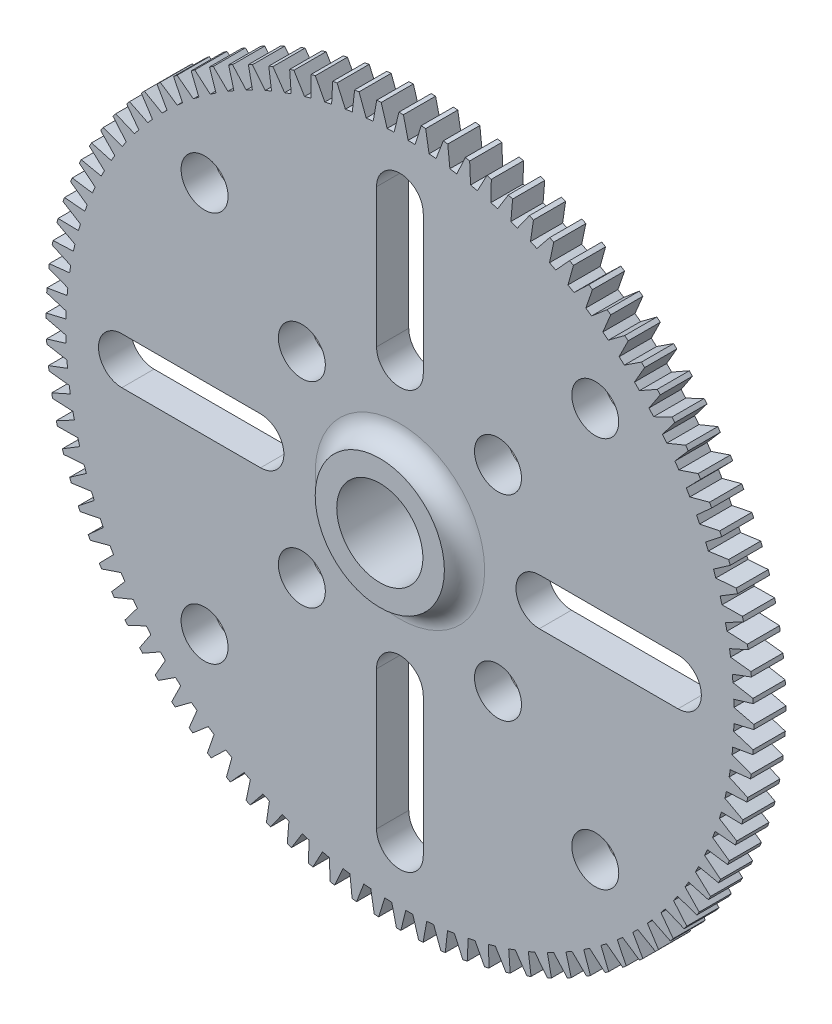
SolidWorks part; units mm, degrees
note: '?' marks a value the reader was unsure of.
ref_plane "Front Plane" through (0, 0, 0) normal (0, 0, 1) x (1, 0, 0)
ref_plane "Top Plane" through (0, 0, 0) normal (0, 1, 0) x (1, 0, 0)
ref_plane "Right Plane" through (0, 0, 0) normal (1, 0, 0) x (0, 0, -1)
sketch "Sketch1" plane through (0, 0, 0) normal (0, 0, 1) x (1, 0, 0)
  circle A0 centre (0, 0) radius 32.1437
  dimension "D1" = 64.2874
extrude "Extrude1" add sketch "Sketch1" along normal blind 2.921
sketch "Sketch3" plane through (0, 0, 0) normal (0, 0, -1) x (-1, 0, 0)
  line L0 (0, 0) -> (0, -32.1437) construction
  line L1 (0, 0) -> (2.2466, -32.0651) construction
  line L2 (0.7438, -30.3376) -> (0.3175, -32.1421)
  line L3 (1.3784, -30.3154) -> (1.9297, -32.0857)
  line L4 (0, 0) -> (1.124, -32.124) construction
  line L5 (0, -32.1437) -> (0.3175, -32.1421) construction
  line L6 (1.9297, -32.0857) -> (2.2466, -32.0651) construction
  circle A0 centre (0, 0) radius 32.1437 construction
  arc A1 (0.3175, -32.1421) -> (1.9297, -32.0857) centre (0, 0) ccw
  arc A2 (0.7438, -30.3376) -> (1.3784, -30.3154) centre (0, 0) ccw
  dimension "D1" = 0.3175
  dimension "D3" = 1.6132
  dimension "D4" = 1.8542
  dimension "D5" = 0.635
extrude "Cut-Extrude1" cut sketch "Sketch3" against normal through all
ref_axis "Axis1" through (0, 0, -30.0023) along (0, 0, 1)?
pattern_circular "CirPattern1" count 100 over 360 about axis through (0, 0, 0) along (0, 0, 1) of "Cut-Extrude1"
sketch "Sketch4" plane through (0, 0, 0) normal (0, 0, -1) x (-1, 0, 0)
  circle A0 centre (0, 0) radius 5.8674
  dimension "D1" = 11.7348
extrude "Extrude2" add sketch "Sketch4" along normal blind 1.8288
fillet "Fillet1" radius 1.8288 1 edges at (5.8674, 0, 0)
ref_plane "Plane1" through (0, 0, 1.4605) normal (0, 0, -1) x (-1, 0, 0)
sketch "Sketch5" plane through (0, 0, -1.8288) normal (0, 0, -1) x (-1, 0, 0)
  circle A0 centre (0, 0) radius 3.9116
  dimension "D1" = 7.8232
mirror "Mirror3" about plane through (0, 0, 1.4605) normal (0, 0, -1) of "Extrude2"
fillet "Fillet2" radius 1.8288 1 edges at (5.8674, 0, 2.921)
extrude "Cut-Extrude3" cut sketch "Sketch5" against normal through all
sketch "Sketch6" plane through (0, 0, 2.921) normal (0, 0, 1) x (1, 0, 0)
  line L0 (0, 0) -> (-33.6773, 0) construction
  line L1 (-25.2603, -2.1209) -> (-12.6619, -2.1209)
  line L3 (-25.2603, 2.1209) -> (-12.6619, 2.1209)
  arc A0 (-25.2603, -2.1209) -> (-25.2603, 2.1209) centre (-25.2603, 0) cw
  arc A1 (-12.6619, -2.1209) -> (-12.6619, 2.1209) centre (-12.6619, 0) ccw
  dimension "D3" = 12.6619
  dimension "D1" = 4.2418
  dimension "D2" = 12.5984
extrude "Cut-Extrude4" cut sketch "Sketch6" against normal up to next
pattern_circular "CirPattern2" count 4 over 360 about axis through (0, 0, 0) along (0, 0, 1) of "Cut-Extrude4"
sketch "Sketch7" plane through (0, 0, 2.921) normal (0, 0, 1) x (1, 0, 0)
  line L0 (0, 0) -> (-35.2734, 35.2734) construction
  circle A0 centre (-8.9084, 8.9084) radius 2.1336
  circle A1 centre (-17.745, 17.745) radius 2.1336
  dimension "D1" = 4.2672
  dimension "D2" = 12.4968
  dimension "D3" = 12.5984
extrude "Cut-Extrude5" cut sketch "Sketch7" against normal up to next
pattern_circular "CirPattern3" count 4 over 360 about axis through (0, 0, 0) along (0, 0, 1) of "Cut-Extrude5"
